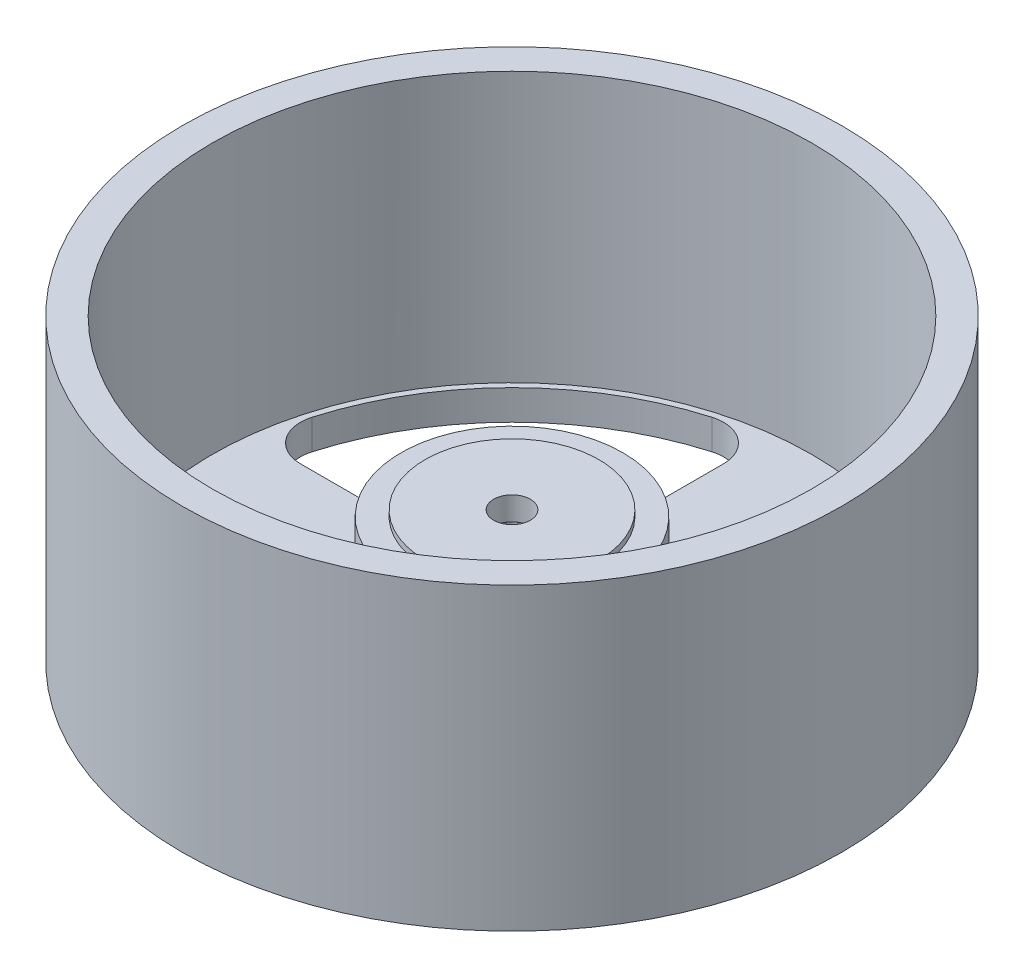
SolidWorks part; units mm, degrees
ref_plane "Front Plane" through (0, 0, 0) normal (0, 0, 1) x (1, 0, 0)
ref_plane "Top Plane" through (0, 0, 0) normal (0, 1, 0) x (1, 0, 0)
ref_plane "Right Plane" through (0, 0, 0) normal (1, 0, 0) x (0, 0, -1)
sketch "Sketch1" plane through (0, 0, 0) normal (0, 1, 0) x (1, 0, 0)
  circle A0 centre (0, 0) radius 27.5
  circle A1 centre (0, 0) radius 25
  dimension "D1" = 55
  dimension "D2" = 2.5
extrude "Boss-Extrude1" add sketch "Sketch1" along normal blind 25
sketch "Sketch2" plane through (0, 0, 0) normal (0, -1, 0) x (1, 0, 0)
  circle A0 centre (0, 0) radius 25
  dimension "D1" = 50
extrude "Boss-Extrude2" add sketch "Sketch2" against normal blind 2.5
sketch "Sketch3" plane through (0, 2.5, 0) normal (0, 1, 0) x (1, 0, 0)
  circle A0 centre (0, 0) radius 7.25
  circle A1 centre (0, 0) radius 9.25
  dimension "D1" = 14.5
  dimension "D2" = 2
extrude "Boss-Extrude3" add sketch "Sketch3" along normal blind 8 from offset 0.5 separate body contours A0
extrude "Boss-Extrude4" add sketch "Sketch3<3>" along normal blind 8
sketch "Sketch3<3>" plane through (0, 2.5, 0) normal (0, 1, 0) x (1, 0, 0) same geometry as "Sketch3"
sketch "Sketch4" plane through (0, 0, 0) normal (0, -1, 0) x (1, 0, 0)
  circle A0 centre (0, 0) radius 7.25
  dimension "D1" = 14.5
extrude "Cut-Extrude1" cut sketch "Sketch4" against normal blind 3
sketch "Sketch5" plane through (0, 0, 0) normal (0, -1, 0) x (1, 0, 0)
  line L0 (7.25, 0) -> (27.5, 0) construction
  line L1 (0, -7.25) -> (0, -27.5) construction
  line L2 (11.8137, -3) -> (20.6458, -3)
  line L3 (3, -11.8137) -> (3, -20.6458)
  line L4 (3, -9.8011) -> (3, -24.3156) construction
  line L5 (9.8011, -3) -> (24.3156, -3) construction
  line L6 (-3, -11.8137) -> (-3, -20.6458)
  line L7 (-11.8137, -3) -> (-20.6458, -3)
  line L8 (-11.8137, 3) -> (-20.6458, 3)
  line L9 (-3, 11.8137) -> (-3, 20.6458)
  line L10 (3, 11.8137) -> (3, 20.6458)
  line L11 (11.8137, 3) -> (20.6458, 3)
  circle A0 centre (0, 0) radius 27.5 construction
  arc A1 (27.5, 0) -> (0, -27.5) centre (0, 0) cw construction
  arc A2 (0, -7.25) -> (7.25, 0) centre (0, 0) ccw construction
  circle A3 centre (0, 0) radius 7.25 construction
  arc A5 (23.5266, -6.8372) -> (6.8372, -23.5266) centre (0, 0) cw
  arc A6 (4.6415, -9.1389) -> (9.1389, -4.6415) centre (0, 0) ccw
  arc A7 (24.3156, -3) -> (3, -24.3156) centre (0, 0) cw construction
  arc A8 (6.8372, -23.5266) -> (3, -20.6458) centre (6, -20.6458) cw
  arc A9 (20.6458, -3) -> (23.5266, -6.8372) centre (20.6458, -6) cw
  arc A10 (3, -9.8011) -> (9.8011, -3) centre (0, 0) ccw construction
  arc A11 (11.8137, -3) -> (9.1389, -4.6415) centre (11.8137, -6) ccw
  arc A12 (3, -11.8137) -> (4.6415, -9.1389) centre (6, -11.8137) cw
  arc A13 (-3, -11.8137) -> (-4.6415, -9.1389) centre (-6, -11.8137) ccw
  arc A14 (-3, -20.6458) -> (-6.8372, -23.5266) centre (-6, -20.6458) cw
  arc A15 (-6.8372, -23.5266) -> (-23.5266, -6.8372) centre (0, 0) cw
  arc A16 (-23.5266, -6.8372) -> (-20.6458, -3) centre (-20.6458, -6) cw
  arc A17 (-11.8137, -3) -> (-9.1389, -4.6415) centre (-11.8137, -6) cw
  arc A18 (-9.1389, -4.6415) -> (-4.6415, -9.1389) centre (0, 0) ccw
  arc A19 (-11.8137, 3) -> (-9.1389, 4.6415) centre (-11.8137, 6) ccw
  arc A20 (-20.6458, 3) -> (-23.5266, 6.8372) centre (-20.6458, 6) cw
  arc A21 (-23.5266, 6.8372) -> (-6.8372, 23.5266) centre (0, 0) cw
  arc A22 (-6.8372, 23.5266) -> (-3, 20.6458) centre (-6, 20.6458) cw
  arc A23 (-3, 11.8137) -> (-4.6415, 9.1389) centre (-6, 11.8137) cw
  arc A24 (-4.6415, 9.1389) -> (-9.1389, 4.6415) centre (0, 0) ccw
  arc A25 (3, 11.8137) -> (4.6415, 9.1389) centre (6, 11.8137) ccw
  arc A26 (3, 20.6458) -> (6.8372, 23.5266) centre (6, 20.6458) cw
  arc A27 (6.8372, 23.5266) -> (23.5266, 6.8372) centre (0, 0) cw
  arc A28 (23.5266, 6.8372) -> (20.6458, 3) centre (20.6458, 6) cw
  arc A29 (11.8137, 3) -> (9.1389, 4.6415) centre (11.8137, 6) cw
  arc A30 (9.1389, 4.6415) -> (4.6415, 9.1389) centre (0, 0) ccw
  point P7 (0, 0)
  point P70 (0, 0)
  dimension "D1" = 3
  dimension "D3" = 3
  dimension "D2" = 90
  dimension "D4" = 4
extrude "Cut-Extrude3" cut sketch "Sketch5" against normal blind 6
sketch "Sketch6" plane through (0, 3, 0) normal (0, -1, 0) x (1, 0, 0)
  line L1 (-3, -3) -> (3, -3)
  line L2 (-3, -3) -> (-3, 3)
  line L3 (-3, 3) -> (3, 3)
  line L4 (3, -3) -> (3, 3)
  line L5 (-3, -3) -> (3, 3) construction
  line L6 (-3, 3) -> (3, -3) construction
  circle A0 centre (3, 3) radius 0.5
  circle A1 centre (-3, -3) radius 0.5
  point P0 (0, 0)
  dimension "D2" = 1
  dimension "D3" = 1
  dimension "D1" = 6
extrude "Cut-Extrude5" cut sketch "Sketch6" against normal blind 6.05 contours A1 L1 L4 A0 L3 L2 | L4 A0 L3 | L2 A1 L1 | L1 A1 L2 | L3 A0 L4 region at (-2.7878, 3, -2.7878) region at (-3.0707, 3, -3.0707) region at (0, 3, 0) region at (2.7878, 3, 2.7878) region at (3.0707, 3, 3.0707)
sketch "Sketch7" plane through (0, 9.05, 0) normal (0, -1, 0) x (1, 0, 0)
  circle A0 centre (0, 0) radius 1.525
  dimension "D1" = 3.05
extrude "Cut-Extrude6" cut sketch "Sketch7" against normal blind 6.05
